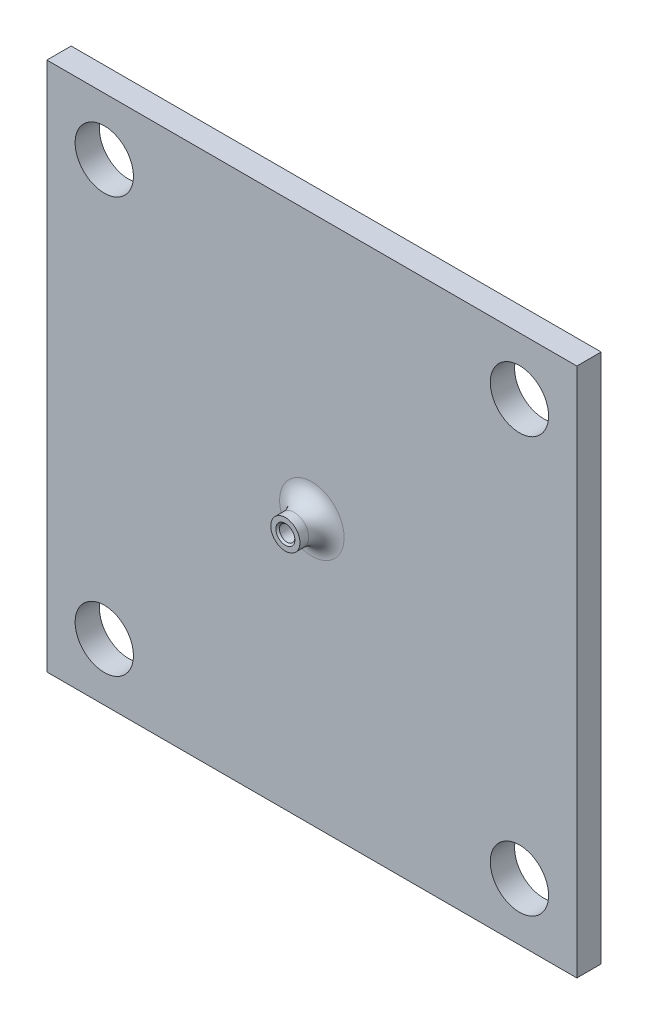
SolidWorks part; units mm, degrees
ref_plane "Piano frontale" through (0, 0, 0) normal (0, 0, 1) x (1, 0, 0)
ref_plane "Piano superiore" through (0, 0, 0) normal (0, 1, 0) x (1, 0, 0)
ref_plane "Piano destro" through (0, 0, 0) normal (1, 0, 0) x (0, 0, -1)
sketch "Sketch1" plane through (0, 0, 0) normal (0, 0, 1) x (1, 0, 0)
  line L0 (-30, 30) -> (-10, 30)
  line L1 (0, 30) -> (-10, 30)
  line L2 (30, 30) -> (30, -30)
  line L3 (30, -30) -> (10, -30)
  line L4 (-30, 30) -> (-30, -30)
  line L5 (10, -30) -> (0, -30)
  line L10 (0, 30) -> (30, 30)
  line L11 (0, -30) -> (-30, -30)
  circle A0 centre (-23.5, 23.5) radius 3.3
  circle A3 centre (-23.5, -23.5) radius 3.3
  circle A4 centre (23.5, -23.5) radius 3.3
  circle A5 centre (23.5, 23.5) radius 3.3
  point P0 (0, 0)
  dimension "D1" = 60
  dimension "D3" = 6.6
  dimension "D2" = 60
extrude "Boss-Extrude1" add sketch "Sketch1" along normal blind 0.75
sketch "Sketch2" plane through (0, 0, 0.75) normal (0, 0, 1) x (1, 0, 0)
  circle A0 centre (0, 0) radius 1
  dimension "D1" = 2
sketch "Sketch3" plane through (0, 0, 0) normal (0, 0, -1) x (-1, 0, 0)
  circle A0 centre (0, 0) radius 11.25
  dimension "D1" = 22.5
loft "Cut-Loft1" cut profiles "Sketch2", "Sketch3" connector at (0.385, 0.9229, 0.75) connector at (-2.1497, 11.0427, 0)
sketch "Sketch4" plane through (0, 0, 0) normal (0, 0, -1) x (-1, 0, 0)
  circle A0 centre (0, 0) radius 23.5
  circle A1 centre (0, 0) radius 11.25
  dimension "D1" = 47
  dimension "D2" = 22.5
extrude "Boss-Extrude2" add sketch "Sketch4" along normal blind 1
sketch "Sketch5" plane through (0, 0, 0.75) normal (0, 0, 1) x (1, 0, 0)
  circle A0 centre (0, 0) radius 0.875
  circle A1 centre (0, 0) radius 1.65
  dimension "D1" = 3.3
  dimension "D2" = 1.75
extrude "Boss-Extrude3" add sketch "Sketch5" along normal blind 5
fillet "Fillet1" radius 4 1 edges at (1.65, 0, 0.75)
fillet "Fillet2" radius 5 1 edges at (-11.25, 0, 0)
sketch "Sketch6" plane through (0, 0, -1) normal (0, 0, -1) x (-1, 0, 0)
  circle A0 centre (0, 0) radius 17.35
  circle A1 centre (0, 0) radius 19.15
  dimension "D1" = 34.7
  dimension "D2" = 38.3
extrude "Cut-Extrude1" cut sketch "Sketch6" against normal blind 1.3
sketch "Sketch7" plane through (0, 0, 0.75) normal (0, 0, 1) x (1, 0, 0)
  line L4 (-30, -30) -> (30, -30)
  line L5 (30, -30) -> (30, 30)
  line L6 (30, 30) -> (-30, 30)
  line L7 (-30, 30) -> (-30, -30)
  line L8 (-30, -30) -> (30, -30)
  line L9 (30, -30) -> (30, 30)
  line L10 (30, 30) -> (-30, 30)
  line L11 (-30, 30) -> (-30, -30)
  circle A0 centre (23.5, 23.5) radius 3.3 construction
  circle A1 centre (23.5, -23.5) radius 3.3 construction
  circle A2 centre (-23.5, 23.5) radius 3.3 construction
  circle A3 centre (-23.5, -23.5) radius 3.3 construction
  circle A4 centre (23.5, 23.5) radius 3.3
  circle A5 centre (23.5, -23.5) radius 3.3
  circle A6 centre (-23.5, 23.5) radius 3.3
  circle A7 centre (-23.5, -23.5) radius 3.3
  dimension "D1" = 0
extrude "Boss-Extrude5" add sketch "Sketch7" along normal blind 2
fillet "Fillet3" radius 2 1 edges at (-2.1859, 0, 2.75)
sketch "Sketch11" plane through (0, 0, 2.75) normal (0, 0, 1) x (1, 0, 0)
  circle A0 centre (0, 0) radius 0.8
  dimension "D1" = 1.6
extrude "Cut-Extrude2" cut sketch "Sketch11" against normal through all
chamfer "Chamfer1" distance 0.2 angle 45 1 edges at (0.875, 0, 5.75)
sketch "Sketch13" plane through (0, 0, 5.75) normal (0, 0, 1) x (1, 0, 0)
